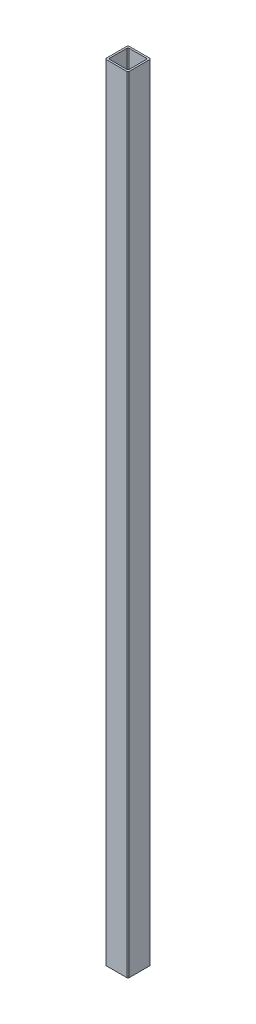
SolidWorks part; units mm, degrees
material "Hexcel AS4C (3000 Filaments)"
ref_plane "Front Plane" through (0, 0, 0) normal (0, 0, 1) x (1, 0, 0)
ref_plane "Top Plane" through (0, 0, 0) normal (0, 1, 0) x (1, 0, 0)
ref_plane "Right Plane" through (0, 0, 0) normal (1, 0, 0) x (0, 0, -1)
sketch "Sketch1" plane through (0, 0, 0) normal (0, 1, 0) x (1, 0, 0)
  line L1 (-9, -10) -> (9, -10)
  line L2 (-10, -9) -> (-10, 9)
  line L3 (-9, 10) -> (9, 10)
  line L4 (10, -9) -> (10, 9)
  line L5 (-10, -10) -> (10, 10) construction
  line L6 (-10, 10) -> (10, -10) construction
  line L7 (-7.5, -8.5) -> (7.5, -8.5)
  line L8 (-8.5, -7.5) -> (-8.5, 7.5)
  line L9 (-7.5, 8.5) -> (7.5, 8.5)
  line L10 (8.5, -7.5) -> (8.5, 7.5)
  line L11 (-8.5, -8.5) -> (8.5, 8.5) construction
  line L12 (-8.5, 8.5) -> (8.5, -8.5) construction
  arc A0 (-9, -10) -> (-10, -9) centre (-9, -9) cw
  arc A1 (9, 10) -> (10, 9) centre (9, 9) cw
  arc A2 (9, -10) -> (10, -9) centre (9, -9) ccw
  arc A3 (-10, 9) -> (-9, 10) centre (-9, 9) cw
  arc A4 (-7.5, -8.5) -> (-8.5, -7.5) centre (-7.5, -7.5) cw
  arc A5 (7.5, -8.5) -> (8.5, -7.5) centre (7.5, -7.5) ccw
  arc A6 (7.5, 8.5) -> (8.5, 7.5) centre (7.5, 7.5) cw
  arc A7 (-8.5, 7.5) -> (-7.5, 8.5) centre (-7.5, 7.5) cw
  point P0 (0, 0)
  point P18 (0, 0)
  dimension "D3" = 1
  dimension "D6" = 1
  dimension "D7" = 1
  dimension "D8" = 1
  dimension "D9" = 1
  dimension "D1" = 20
  dimension "D2" = 20
  dimension "D4" = 17
  dimension "D5" = 17
extrude "Boss-Extrude1" add sketch "Sketch1" along normal blind 685
